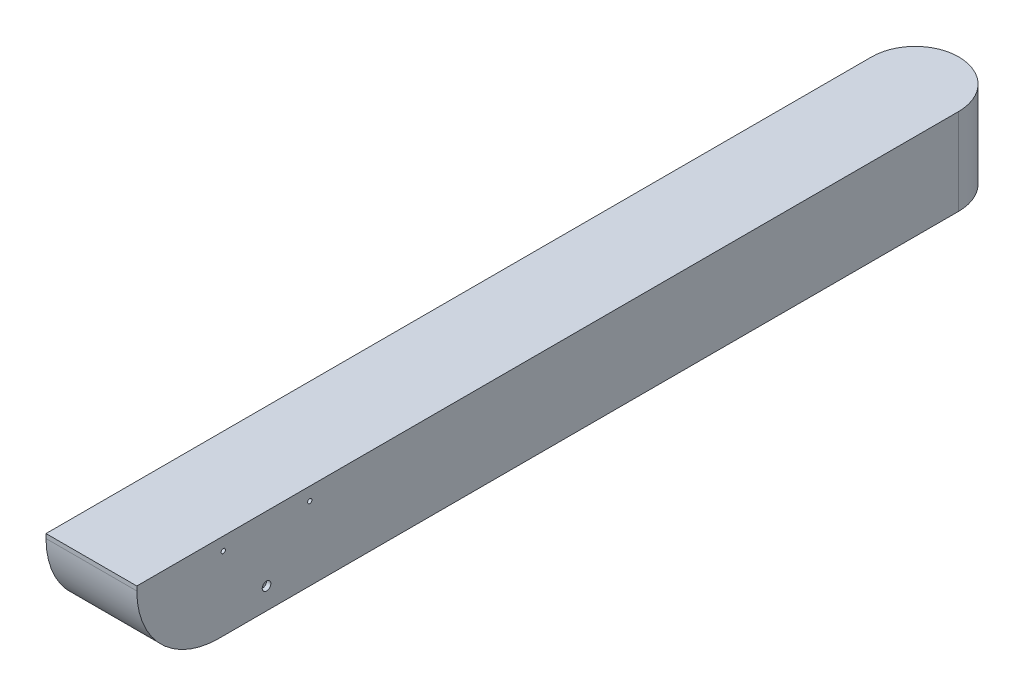
SolidWorks part; units mm, degrees
ref_plane "Front Plane" through (0, 0, 0) normal (0, 0, 1) x (1, 0, 0)
ref_plane "Top Plane" through (0, 0, 0) normal (0, 1, 0) x (1, 0, 0)
ref_plane "Right Plane" through (0, 0, 0) normal (1, 0, 0) x (0, 0, -1)
sketch "Sketch1" plane through (0, 0, 0) normal (0, 1, 0) x (1, 0, 0)
  line L0 (0, 0) -> (0, -2010)
  line L1 (0, -2010) -> (210, -2010)
  line L3 (210, -2010) -> (210, 0)
  line L4 (210, 0) -> (0, 0)
  dimension "D1" = 2010
  dimension "D2" = 210
extrude "Boss-Extrude1" add sketch "Sketch1" along normal blind 200 contours L3 L4 L0 L1
fillet "Fillet1" radius 110 1 edges at (210, 100, 0) type face fillet first side face at (210, 100, 1005) second side face at (105, 100, 0)
fillet "Fillet2" radius 100 1 edges at (0, 100, 0) type face fillet first side face at (0, 100, 1005) second side face at (50, 100, 0)
fillet "Fillet3" radius 190 1 edges at (105, 0, 2010)
sketch "Sketch3" plane through (210, 0, 0) normal (1, 0, 0) x (0, 0, -1)
  line L0 (-1820, 0) -> (-110, 0) construction
  line L1 (-2010, 200) -> (-2010, 190) construction
  circle A0 centre (-1710, 50) radius 10
  dimension "D1" = 20
  dimension "D2" = 50
  dimension "D3" = 300
extrude "Cut-Extrude1" cut sketch "Sketch3" against normal blind 10
sketch "Sketch4" plane through (210, 0, 0) normal (1, 0, 0) x (0, 0, -1)
  line L0 (-1610, 170) -> (-1810, 170)
  line L1 (-2010, 200) -> (-110, 200) construction
  line L2 (-2010, 200) -> (-2010, 190) construction
  circle A0 centre (-1810, 170) radius 5
  circle A1 centre (-1610, 170) radius 5
  dimension "D4" = 10
  dimension "D5" = 10
  dimension "D1" = 30
  dimension "D2" = 200
  dimension "D3" = 200
extrude "Cut-Extrude2" cut sketch "Sketch4" against normal through all contours A1 | A0 region at (210, 174.8586, 1610)
